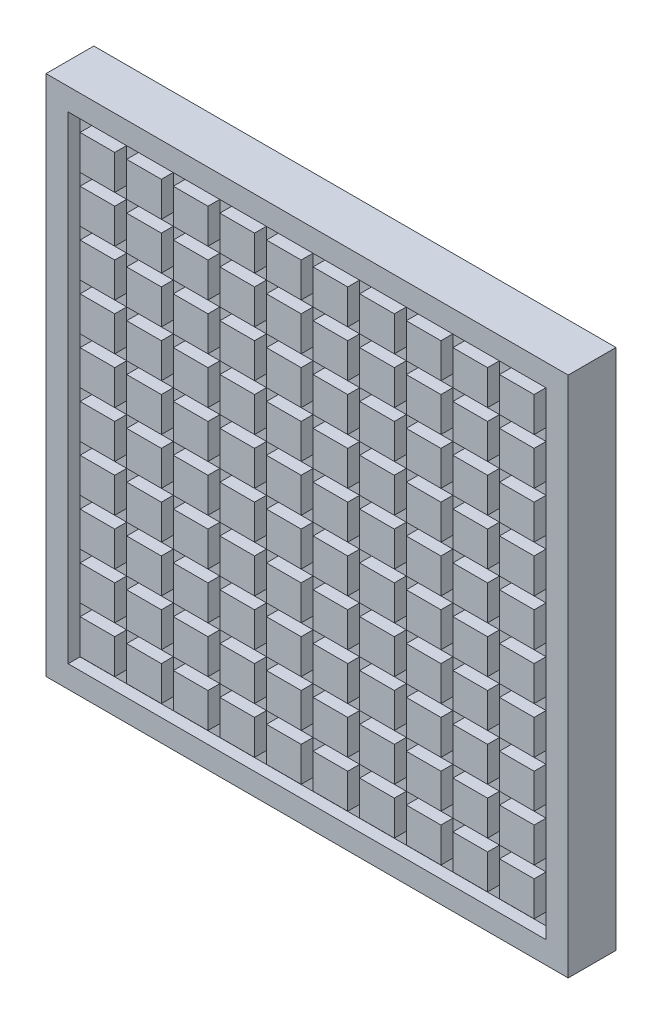
SolidWorks part; units mm, degrees
ref_plane "前视基准面" through (0, 0, 0) normal (0, 0, 1) x (1, 0, 0)
ref_plane "上视基准面" through (0, 0, 0) normal (0, 1, 0) x (1, 0, 0)
ref_plane "右视基准面" through (0, 0, 0) normal (1, 0, 0) x (0, 0, -1)
other "Configuration Table"
sketch "草图1" plane through (0, 0, 0) normal (0, 0, 1) x (1, 0, 0)
  line L1 (0, 0) -> (437, 0)
  line L2 (0, 0) -> (0, 437)
  line L3 (0, 437) -> (437, 437)
  line L4 (437, 0) -> (437, 437)
extrude "凸台-拉伸1" add sketch "草图1" along normal blind 40
ref_point "点2"
sketch "草图2" plane through (0, 0, 0) normal (-1, 0, 0) x (0, 0, 1)
  line L0 (20, 218.5) -> (8.3215, 218.5)
ref_axis "基准轴1" through (0, 218.5, 20) along (0, 0, -1)
ref_axis "基准轴2" through (0, 218.5, 20) along (-1, 0, 0)
sketch "草图3" plane through (0, 0, 40) normal (0, 0, 1) x (1, 0, 0)
  line L25 (18.5, 418.5) -> (418.5, 418.5)
  line L26 (18.5, 418.5) -> (18.5, 18.5)
  line L27 (18.5, 18.5) -> (418.5, 18.5)
  line L28 (418.5, 418.5) -> (418.5, 18.5)
extrude "切除-拉伸1" cut sketch "草图3" against normal blind 10
sketch "草图4" plane through (0, 0, 30) normal (0, 0, 1) x (1, 0, 0)
  line L0 (67.5, 408.6283) -> (67.5, 379.6283)
  line L5 (28.5, 408.6283) -> (57.5, 408.6283)
  line L6 (28.5, 408.6283) -> (28.5, 379.6283)
  line L7 (28.5, 379.6283) -> (57.5, 379.6283)
  line L8 (57.5, 408.6283) -> (57.5, 379.6283)
  line L9 (67.5, 408.6283) -> (96.5, 408.6283)
  line L10 (96.5, 408.6283) -> (96.5, 379.6283)
  line L11 (67.5, 379.6283) -> (96.5, 379.6283)
  line L12 (106.5, 408.6283) -> (106.5, 379.6283)
  line L13 (106.5, 408.6283) -> (135.5, 408.6283)
  line L14 (135.5, 408.6283) -> (135.5, 379.6283)
  line L15 (106.5, 379.6283) -> (135.5, 379.6283)
  line L16 (145.5, 408.6283) -> (145.5, 379.6283)
  line L17 (145.5, 408.6283) -> (174.5, 408.6283)
  line L18 (174.5, 408.6283) -> (174.5, 379.6283)
  line L19 (145.5, 379.6283) -> (174.5, 379.6283)
  line L20 (184.5, 408.6283) -> (184.5, 379.6283)
  line L21 (184.5, 408.6283) -> (213.5, 408.6283)
  line L22 (213.5, 408.6283) -> (213.5, 379.6283)
  line L23 (184.5, 379.6283) -> (213.5, 379.6283)
  line L24 (223.5, 408.6283) -> (223.5, 379.6283)
  line L25 (223.5, 408.6283) -> (252.5, 408.6283)
  line L26 (252.5, 408.6283) -> (252.5, 379.6283)
  line L27 (223.5, 379.6283) -> (252.5, 379.6283)
  line L28 (262.5, 408.6283) -> (262.5, 379.6283)
  line L29 (262.5, 408.6283) -> (291.5, 408.6283)
  line L30 (291.5, 408.6283) -> (291.5, 379.6283)
  line L31 (262.5, 379.6283) -> (291.5, 379.6283)
  line L32 (301.5, 408.6283) -> (301.5, 379.6283)
  line L33 (301.5, 408.6283) -> (330.5, 408.6283)
  line L34 (330.5, 408.6283) -> (330.5, 379.6283)
  line L35 (301.5, 379.6283) -> (330.5, 379.6283)
  line L36 (340.5, 408.6283) -> (340.5, 379.6283)
  line L37 (340.5, 408.6283) -> (369.5, 408.6283)
  line L38 (369.5, 408.6283) -> (369.5, 379.6283)
  line L39 (340.5, 379.6283) -> (369.5, 379.6283)
  line L40 (379.5, 408.6283) -> (379.5, 379.6283)
  line L41 (379.5, 408.6283) -> (408.5, 408.6283)
  line L42 (408.5, 408.6283) -> (408.5, 379.6283)
  line L43 (379.5, 379.6283) -> (408.5, 379.6283)
  line L44 (67.5, 369.6283) -> (67.5, 340.6283)
  line L45 (67.5, 369.6283) -> (96.5, 369.6283)
  line L46 (96.5, 369.6283) -> (96.5, 340.6283)
  line L47 (67.5, 340.6283) -> (96.5, 340.6283)
  line L48 (106.5, 369.6283) -> (106.5, 340.6283)
  line L49 (106.5, 369.6283) -> (135.5, 369.6283)
  line L50 (135.5, 369.6283) -> (135.5, 340.6283)
  line L51 (106.5, 340.6283) -> (135.5, 340.6283)
  line L52 (145.5, 369.6283) -> (145.5, 340.6283)
  line L53 (145.5, 369.6283) -> (174.5, 369.6283)
  line L54 (174.5, 369.6283) -> (174.5, 340.6283)
  line L55 (145.5, 340.6283) -> (174.5, 340.6283)
  line L56 (184.5, 369.6283) -> (184.5, 340.6283)
  line L57 (184.5, 369.6283) -> (213.5, 369.6283)
  line L58 (213.5, 369.6283) -> (213.5, 340.6283)
  line L59 (184.5, 340.6283) -> (213.5, 340.6283)
  line L60 (223.5, 369.6283) -> (223.5, 340.6283)
  line L61 (223.5, 369.6283) -> (252.5, 369.6283)
  line L62 (252.5, 369.6283) -> (252.5, 340.6283)
  line L63 (223.5, 340.6283) -> (252.5, 340.6283)
  line L64 (262.5, 369.6283) -> (262.5, 340.6283)
  line L65 (262.5, 369.6283) -> (291.5, 369.6283)
  line L66 (291.5, 369.6283) -> (291.5, 340.6283)
  line L67 (262.5, 340.6283) -> (291.5, 340.6283)
  line L68 (301.5, 369.6283) -> (301.5, 340.6283)
  line L69 (301.5, 369.6283) -> (330.5, 369.6283)
  line L70 (330.5, 369.6283) -> (330.5, 340.6283)
  line L71 (301.5, 340.6283) -> (330.5, 340.6283)
  line L72 (340.5, 369.6283) -> (340.5, 340.6283)
  line L73 (340.5, 369.6283) -> (369.5, 369.6283)
  line L74 (369.5, 369.6283) -> (369.5, 340.6283)
  line L75 (340.5, 340.6283) -> (369.5, 340.6283)
  line L76 (379.5, 369.6283) -> (379.5, 340.6283)
  line L77 (379.5, 369.6283) -> (408.5, 369.6283)
  line L78 (408.5, 369.6283) -> (408.5, 340.6283)
  line L79 (379.5, 340.6283) -> (408.5, 340.6283)
  line L80 (67.5, 330.6283) -> (67.5, 301.6283)
  line L81 (67.5, 330.6283) -> (96.5, 330.6283)
  line L82 (96.5, 330.6283) -> (96.5, 301.6283)
  line L83 (67.5, 301.6283) -> (96.5, 301.6283)
  line L84 (106.5, 330.6283) -> (106.5, 301.6283)
  line L85 (106.5, 330.6283) -> (135.5, 330.6283)
  line L86 (135.5, 330.6283) -> (135.5, 301.6283)
  line L87 (106.5, 301.6283) -> (135.5, 301.6283)
  line L88 (145.5, 330.6283) -> (145.5, 301.6283)
  line L89 (145.5, 330.6283) -> (174.5, 330.6283)
  line L90 (174.5, 330.6283) -> (174.5, 301.6283)
  line L91 (145.5, 301.6283) -> (174.5, 301.6283)
  line L92 (184.5, 330.6283) -> (184.5, 301.6283)
  line L93 (184.5, 330.6283) -> (213.5, 330.6283)
  line L94 (213.5, 330.6283) -> (213.5, 301.6283)
  line L95 (184.5, 301.6283) -> (213.5, 301.6283)
  line L96 (223.5, 330.6283) -> (223.5, 301.6283)
  line L97 (223.5, 330.6283) -> (252.5, 330.6283)
  line L98 (252.5, 330.6283) -> (252.5, 301.6283)
  line L99 (223.5, 301.6283) -> (252.5, 301.6283)
  line L100 (262.5, 330.6283) -> (262.5, 301.6283)
  line L101 (262.5, 330.6283) -> (291.5, 330.6283)
  line L102 (291.5, 330.6283) -> (291.5, 301.6283)
  line L103 (262.5, 301.6283) -> (291.5, 301.6283)
  line L104 (301.5, 330.6283) -> (301.5, 301.6283)
  line L105 (301.5, 330.6283) -> (330.5, 330.6283)
  line L106 (330.5, 330.6283) -> (330.5, 301.6283)
  line L107 (301.5, 301.6283) -> (330.5, 301.6283)
  line L108 (340.5, 330.6283) -> (340.5, 301.6283)
  line L109 (340.5, 330.6283) -> (369.5, 330.6283)
  line L110 (369.5, 330.6283) -> (369.5, 301.6283)
  line L111 (340.5, 301.6283) -> (369.5, 301.6283)
  line L112 (379.5, 330.6283) -> (379.5, 301.6283)
  line L113 (379.5, 330.6283) -> (408.5, 330.6283)
  line L114 (408.5, 330.6283) -> (408.5, 301.6283)
  line L115 (379.5, 301.6283) -> (408.5, 301.6283)
  line L116 (67.5, 291.6283) -> (67.5, 262.6283)
  line L117 (67.5, 291.6283) -> (96.5, 291.6283)
  line L118 (96.5, 291.6283) -> (96.5, 262.6283)
  line L119 (67.5, 262.6283) -> (96.5, 262.6283)
  line L120 (106.5, 291.6283) -> (106.5, 262.6283)
  line L121 (106.5, 291.6283) -> (135.5, 291.6283)
  line L122 (135.5, 291.6283) -> (135.5, 262.6283)
  line L123 (106.5, 262.6283) -> (135.5, 262.6283)
  line L124 (145.5, 291.6283) -> (145.5, 262.6283)
  line L125 (145.5, 291.6283) -> (174.5, 291.6283)
  line L126 (174.5, 291.6283) -> (174.5, 262.6283)
  line L127 (145.5, 262.6283) -> (174.5, 262.6283)
  line L128 (184.5, 291.6283) -> (184.5, 262.6283)
  line L129 (184.5, 291.6283) -> (213.5, 291.6283)
  line L130 (213.5, 291.6283) -> (213.5, 262.6283)
  line L131 (184.5, 262.6283) -> (213.5, 262.6283)
  line L132 (223.5, 291.6283) -> (223.5, 262.6283)
  line L133 (223.5, 291.6283) -> (252.5, 291.6283)
  line L134 (252.5, 291.6283) -> (252.5, 262.6283)
  line L135 (223.5, 262.6283) -> (252.5, 262.6283)
  line L136 (262.5, 291.6283) -> (262.5, 262.6283)
  line L137 (262.5, 291.6283) -> (291.5, 291.6283)
  line L138 (291.5, 291.6283) -> (291.5, 262.6283)
  line L139 (262.5, 262.6283) -> (291.5, 262.6283)
  line L140 (301.5, 291.6283) -> (301.5, 262.6283)
  line L141 (301.5, 291.6283) -> (330.5, 291.6283)
  line L142 (330.5, 291.6283) -> (330.5, 262.6283)
  line L143 (301.5, 262.6283) -> (330.5, 262.6283)
  line L144 (340.5, 291.6283) -> (340.5, 262.6283)
  line L145 (340.5, 291.6283) -> (369.5, 291.6283)
  line L146 (369.5, 291.6283) -> (369.5, 262.6283)
  line L147 (340.5, 262.6283) -> (369.5, 262.6283)
  line L148 (379.5, 291.6283) -> (379.5, 262.6283)
  line L149 (379.5, 291.6283) -> (408.5, 291.6283)
  line L150 (408.5, 291.6283) -> (408.5, 262.6283)
  line L151 (379.5, 262.6283) -> (408.5, 262.6283)
  line L152 (67.5, 252.6283) -> (67.5, 223.6283)
  line L153 (67.5, 252.6283) -> (96.5, 252.6283)
  line L154 (96.5, 252.6283) -> (96.5, 223.6283)
  line L155 (67.5, 223.6283) -> (96.5, 223.6283)
  line L156 (106.5, 252.6283) -> (106.5, 223.6283)
  line L157 (106.5, 252.6283) -> (135.5, 252.6283)
  line L158 (135.5, 252.6283) -> (135.5, 223.6283)
  line L159 (106.5, 223.6283) -> (135.5, 223.6283)
  line L160 (145.5, 252.6283) -> (145.5, 223.6283)
  line L161 (145.5, 252.6283) -> (174.5, 252.6283)
  line L162 (174.5, 252.6283) -> (174.5, 223.6283)
  line L163 (145.5, 223.6283) -> (174.5, 223.6283)
  line L164 (184.5, 252.6283) -> (184.5, 223.6283)
  line L165 (184.5, 252.6283) -> (213.5, 252.6283)
  line L166 (213.5, 252.6283) -> (213.5, 223.6283)
  line L167 (184.5, 223.6283) -> (213.5, 223.6283)
  line L168 (223.5, 252.6283) -> (223.5, 223.6283)
  line L169 (223.5, 252.6283) -> (252.5, 252.6283)
  line L170 (252.5, 252.6283) -> (252.5, 223.6283)
  line L171 (223.5, 223.6283) -> (252.5, 223.6283)
  line L172 (262.5, 252.6283) -> (262.5, 223.6283)
  line L173 (262.5, 252.6283) -> (291.5, 252.6283)
  line L174 (291.5, 252.6283) -> (291.5, 223.6283)
  line L175 (262.5, 223.6283) -> (291.5, 223.6283)
  line L176 (301.5, 252.6283) -> (301.5, 223.6283)
  line L177 (301.5, 252.6283) -> (330.5, 252.6283)
  line L178 (330.5, 252.6283) -> (330.5, 223.6283)
  line L179 (301.5, 223.6283) -> (330.5, 223.6283)
  line L180 (340.5, 252.6283) -> (340.5, 223.6283)
  line L181 (340.5, 252.6283) -> (369.5, 252.6283)
  line L182 (369.5, 252.6283) -> (369.5, 223.6283)
  line L183 (340.5, 223.6283) -> (369.5, 223.6283)
  line L184 (379.5, 252.6283) -> (379.5, 223.6283)
  line L185 (379.5, 252.6283) -> (408.5, 252.6283)
  line L186 (408.5, 252.6283) -> (408.5, 223.6283)
  line L187 (379.5, 223.6283) -> (408.5, 223.6283)
  line L188 (67.5, 213.6283) -> (67.5, 184.6283)
  line L189 (67.5, 213.6283) -> (96.5, 213.6283)
  line L190 (96.5, 213.6283) -> (96.5, 184.6283)
  line L191 (67.5, 184.6283) -> (96.5, 184.6283)
  line L192 (106.5, 213.6283) -> (106.5, 184.6283)
  line L193 (106.5, 213.6283) -> (135.5, 213.6283)
  line L194 (135.5, 213.6283) -> (135.5, 184.6283)
  line L195 (106.5, 184.6283) -> (135.5, 184.6283)
  line L196 (145.5, 213.6283) -> (145.5, 184.6283)
  line L197 (145.5, 213.6283) -> (174.5, 213.6283)
  line L198 (174.5, 213.6283) -> (174.5, 184.6283)
  line L199 (145.5, 184.6283) -> (174.5, 184.6283)
  line L200 (184.5, 213.6283) -> (184.5, 184.6283)
  line L201 (184.5, 213.6283) -> (213.5, 213.6283)
  line L202 (213.5, 213.6283) -> (213.5, 184.6283)
  line L203 (184.5, 184.6283) -> (213.5, 184.6283)
  line L204 (223.5, 213.6283) -> (223.5, 184.6283)
  line L205 (223.5, 213.6283) -> (252.5, 213.6283)
  line L206 (252.5, 213.6283) -> (252.5, 184.6283)
  line L207 (223.5, 184.6283) -> (252.5, 184.6283)
  line L208 (262.5, 213.6283) -> (262.5, 184.6283)
  line L209 (262.5, 213.6283) -> (291.5, 213.6283)
  line L210 (291.5, 213.6283) -> (291.5, 184.6283)
  line L211 (262.5, 184.6283) -> (291.5, 184.6283)
  line L212 (301.5, 213.6283) -> (301.5, 184.6283)
  line L213 (301.5, 213.6283) -> (330.5, 213.6283)
  line L214 (330.5, 213.6283) -> (330.5, 184.6283)
  line L215 (301.5, 184.6283) -> (330.5, 184.6283)
  line L216 (340.5, 213.6283) -> (340.5, 184.6283)
  line L217 (340.5, 213.6283) -> (369.5, 213.6283)
  line L218 (369.5, 213.6283) -> (369.5, 184.6283)
  line L219 (340.5, 184.6283) -> (369.5, 184.6283)
  line L220 (379.5, 213.6283) -> (379.5, 184.6283)
  line L221 (379.5, 213.6283) -> (408.5, 213.6283)
  line L222 (408.5, 213.6283) -> (408.5, 184.6283)
  line L223 (379.5, 184.6283) -> (408.5, 184.6283)
  line L224 (67.5, 174.6283) -> (67.5, 145.6283)
  line L225 (67.5, 174.6283) -> (96.5, 174.6283)
  line L226 (96.5, 174.6283) -> (96.5, 145.6283)
  line L227 (67.5, 145.6283) -> (96.5, 145.6283)
  line L228 (106.5, 174.6283) -> (106.5, 145.6283)
  line L229 (106.5, 174.6283) -> (135.5, 174.6283)
  line L230 (135.5, 174.6283) -> (135.5, 145.6283)
  line L231 (106.5, 145.6283) -> (135.5, 145.6283)
  line L232 (145.5, 174.6283) -> (145.5, 145.6283)
  line L233 (145.5, 174.6283) -> (174.5, 174.6283)
  line L234 (174.5, 174.6283) -> (174.5, 145.6283)
  line L235 (145.5, 145.6283) -> (174.5, 145.6283)
  line L236 (184.5, 174.6283) -> (184.5, 145.6283)
  line L237 (184.5, 174.6283) -> (213.5, 174.6283)
  line L238 (213.5, 174.6283) -> (213.5, 145.6283)
  line L239 (184.5, 145.6283) -> (213.5, 145.6283)
  line L240 (223.5, 174.6283) -> (223.5, 145.6283)
  line L241 (223.5, 174.6283) -> (252.5, 174.6283)
  line L242 (252.5, 174.6283) -> (252.5, 145.6283)
  line L243 (223.5, 145.6283) -> (252.5, 145.6283)
  line L244 (262.5, 174.6283) -> (262.5, 145.6283)
  line L245 (262.5, 174.6283) -> (291.5, 174.6283)
  line L246 (291.5, 174.6283) -> (291.5, 145.6283)
  line L247 (262.5, 145.6283) -> (291.5, 145.6283)
  line L248 (301.5, 174.6283) -> (301.5, 145.6283)
  line L249 (301.5, 174.6283) -> (330.5, 174.6283)
  line L250 (330.5, 174.6283) -> (330.5, 145.6283)
  line L251 (301.5, 145.6283) -> (330.5, 145.6283)
  line L252 (340.5, 174.6283) -> (340.5, 145.6283)
  line L253 (340.5, 174.6283) -> (369.5, 174.6283)
  line L254 (369.5, 174.6283) -> (369.5, 145.6283)
  line L255 (340.5, 145.6283) -> (369.5, 145.6283)
  line L256 (379.5, 174.6283) -> (379.5, 145.6283)
  line L257 (379.5, 174.6283) -> (408.5, 174.6283)
  line L258 (408.5, 174.6283) -> (408.5, 145.6283)
  line L259 (379.5, 145.6283) -> (408.5, 145.6283)
  line L260 (67.5, 135.6283) -> (67.5, 106.6283)
  line L261 (67.5, 135.6283) -> (96.5, 135.6283)
  line L262 (96.5, 135.6283) -> (96.5, 106.6283)
  line L263 (67.5, 106.6283) -> (96.5, 106.6283)
  line L264 (106.5, 135.6283) -> (106.5, 106.6283)
  line L265 (106.5, 135.6283) -> (135.5, 135.6283)
  line L266 (135.5, 135.6283) -> (135.5, 106.6283)
  line L267 (106.5, 106.6283) -> (135.5, 106.6283)
  line L268 (145.5, 135.6283) -> (145.5, 106.6283)
  line L269 (145.5, 135.6283) -> (174.5, 135.6283)
  line L270 (174.5, 135.6283) -> (174.5, 106.6283)
  line L271 (145.5, 106.6283) -> (174.5, 106.6283)
  line L272 (184.5, 135.6283) -> (184.5, 106.6283)
  line L273 (184.5, 135.6283) -> (213.5, 135.6283)
  line L274 (213.5, 135.6283) -> (213.5, 106.6283)
  line L275 (184.5, 106.6283) -> (213.5, 106.6283)
  line L276 (223.5, 135.6283) -> (223.5, 106.6283)
  line L277 (223.5, 135.6283) -> (252.5, 135.6283)
  line L278 (252.5, 135.6283) -> (252.5, 106.6283)
  line L279 (223.5, 106.6283) -> (252.5, 106.6283)
  line L280 (262.5, 135.6283) -> (262.5, 106.6283)
  line L281 (262.5, 135.6283) -> (291.5, 135.6283)
  line L282 (291.5, 135.6283) -> (291.5, 106.6283)
  line L283 (262.5, 106.6283) -> (291.5, 106.6283)
  line L284 (301.5, 135.6283) -> (301.5, 106.6283)
  line L285 (301.5, 135.6283) -> (330.5, 135.6283)
  line L286 (330.5, 135.6283) -> (330.5, 106.6283)
  line L287 (301.5, 106.6283) -> (330.5, 106.6283)
  line L288 (340.5, 135.6283) -> (340.5, 106.6283)
  line L289 (340.5, 135.6283) -> (369.5, 135.6283)
  line L290 (369.5, 135.6283) -> (369.5, 106.6283)
  line L291 (340.5, 106.6283) -> (369.5, 106.6283)
  line L292 (379.5, 135.6283) -> (379.5, 106.6283)
  line L293 (379.5, 135.6283) -> (408.5, 135.6283)
  line L294 (408.5, 135.6283) -> (408.5, 106.6283)
  line L295 (379.5, 106.6283) -> (408.5, 106.6283)
  line L296 (67.5, 96.6283) -> (67.5, 67.6283)
  line L297 (67.5, 96.6283) -> (96.5, 96.6283)
  line L298 (96.5, 96.6283) -> (96.5, 67.6283)
  line L299 (67.5, 67.6283) -> (96.5, 67.6283)
  line L300 (106.5, 96.6283) -> (106.5, 67.6283)
  line L301 (106.5, 96.6283) -> (135.5, 96.6283)
  line L302 (135.5, 96.6283) -> (135.5, 67.6283)
  line L303 (106.5, 67.6283) -> (135.5, 67.6283)
  line L304 (145.5, 96.6283) -> (145.5, 67.6283)
  line L305 (145.5, 96.6283) -> (174.5, 96.6283)
  line L306 (174.5, 96.6283) -> (174.5, 67.6283)
  line L307 (145.5, 67.6283) -> (174.5, 67.6283)
  line L308 (184.5, 96.6283) -> (184.5, 67.6283)
  line L309 (184.5, 96.6283) -> (213.5, 96.6283)
  line L310 (213.5, 96.6283) -> (213.5, 67.6283)
  line L311 (184.5, 67.6283) -> (213.5, 67.6283)
  line L312 (223.5, 96.6283) -> (223.5, 67.6283)
  line L313 (223.5, 96.6283) -> (252.5, 96.6283)
  line L314 (252.5, 96.6283) -> (252.5, 67.6283)
  line L315 (223.5, 67.6283) -> (252.5, 67.6283)
  line L316 (262.5, 96.6283) -> (262.5, 67.6283)
  line L317 (262.5, 96.6283) -> (291.5, 96.6283)
  line L318 (291.5, 96.6283) -> (291.5, 67.6283)
  line L319 (262.5, 67.6283) -> (291.5, 67.6283)
  line L320 (301.5, 96.6283) -> (301.5, 67.6283)
  line L321 (301.5, 96.6283) -> (330.5, 96.6283)
  line L322 (330.5, 96.6283) -> (330.5, 67.6283)
  line L323 (301.5, 67.6283) -> (330.5, 67.6283)
  line L324 (340.5, 96.6283) -> (340.5, 67.6283)
  line L325 (340.5, 96.6283) -> (369.5, 96.6283)
  line L326 (369.5, 96.6283) -> (369.5, 67.6283)
  line L327 (340.5, 67.6283) -> (369.5, 67.6283)
  line L328 (379.5, 96.6283) -> (379.5, 67.6283)
  line L329 (379.5, 96.6283) -> (408.5, 96.6283)
  line L330 (408.5, 96.6283) -> (408.5, 67.6283)
  line L331 (379.5, 67.6283) -> (408.5, 67.6283)
  line L332 (67.5, 57.6283) -> (67.5, 28.6283)
  line L333 (67.5, 57.6283) -> (96.5, 57.6283)
  line L334 (96.5, 57.6283) -> (96.5, 28.6283)
  line L335 (67.5, 28.6283) -> (96.5, 28.6283)
  line L336 (106.5, 57.6283) -> (106.5, 28.6283)
  line L337 (106.5, 57.6283) -> (135.5, 57.6283)
  line L338 (135.5, 57.6283) -> (135.5, 28.6283)
  line L339 (106.5, 28.6283) -> (135.5, 28.6283)
  line L340 (145.5, 57.6283) -> (145.5, 28.6283)
  line L341 (145.5, 57.6283) -> (174.5, 57.6283)
  line L342 (174.5, 57.6283) -> (174.5, 28.6283)
  line L343 (145.5, 28.6283) -> (174.5, 28.6283)
  line L344 (184.5, 57.6283) -> (184.5, 28.6283)
  line L345 (184.5, 57.6283) -> (213.5, 57.6283)
  line L346 (213.5, 57.6283) -> (213.5, 28.6283)
  line L347 (184.5, 28.6283) -> (213.5, 28.6283)
  line L348 (223.5, 57.6283) -> (223.5, 28.6283)
  line L349 (223.5, 57.6283) -> (252.5, 57.6283)
  line L350 (252.5, 57.6283) -> (252.5, 28.6283)
  line L351 (223.5, 28.6283) -> (252.5, 28.6283)
  line L352 (262.5, 57.6283) -> (262.5, 28.6283)
  line L353 (262.5, 57.6283) -> (291.5, 57.6283)
  line L354 (291.5, 57.6283) -> (291.5, 28.6283)
  line L355 (262.5, 28.6283) -> (291.5, 28.6283)
  line L356 (301.5, 57.6283) -> (301.5, 28.6283)
  line L357 (301.5, 57.6283) -> (330.5, 57.6283)
  line L358 (330.5, 57.6283) -> (330.5, 28.6283)
  line L359 (301.5, 28.6283) -> (330.5, 28.6283)
  line L360 (340.5, 57.6283) -> (340.5, 28.6283)
  line L361 (340.5, 57.6283) -> (369.5, 57.6283)
  line L362 (369.5, 57.6283) -> (369.5, 28.6283)
  line L363 (340.5, 28.6283) -> (369.5, 28.6283)
  line L364 (379.5, 57.6283) -> (379.5, 28.6283)
  line L365 (379.5, 57.6283) -> (408.5, 57.6283)
  line L366 (408.5, 57.6283) -> (408.5, 28.6283)
  line L367 (379.5, 28.6283) -> (408.5, 28.6283)
  line L368 (28.5, 369.6283) -> (28.5, 340.6283)
  line L369 (28.5, 369.6283) -> (57.5, 369.6283)
  line L370 (57.5, 369.6283) -> (57.5, 340.6283)
  line L371 (28.5, 340.6283) -> (57.5, 340.6283)
  line L372 (28.5, 330.6283) -> (28.5, 301.6283)
  line L373 (28.5, 330.6283) -> (57.5, 330.6283)
  line L374 (57.5, 330.6283) -> (57.5, 301.6283)
  line L375 (28.5, 301.6283) -> (57.5, 301.6283)
  line L376 (28.5, 291.6283) -> (28.5, 262.6283)
  line L377 (28.5, 291.6283) -> (57.5, 291.6283)
  line L378 (57.5, 291.6283) -> (57.5, 262.6283)
  line L379 (28.5, 262.6283) -> (57.5, 262.6283)
  line L380 (28.5, 252.6283) -> (28.5, 223.6283)
  line L381 (28.5, 252.6283) -> (57.5, 252.6283)
  line L382 (57.5, 252.6283) -> (57.5, 223.6283)
  line L383 (28.5, 223.6283) -> (57.5, 223.6283)
  line L384 (28.5, 213.6283) -> (28.5, 184.6283)
  line L385 (28.5, 213.6283) -> (57.5, 213.6283)
  line L386 (57.5, 213.6283) -> (57.5, 184.6283)
  line L387 (28.5, 184.6283) -> (57.5, 184.6283)
  line L388 (28.5, 174.6283) -> (28.5, 145.6283)
  line L389 (28.5, 174.6283) -> (57.5, 174.6283)
  line L390 (57.5, 174.6283) -> (57.5, 145.6283)
  line L391 (28.5, 145.6283) -> (57.5, 145.6283)
  line L392 (28.5, 135.6283) -> (28.5, 106.6283)
  line L393 (28.5, 135.6283) -> (57.5, 135.6283)
  line L394 (57.5, 135.6283) -> (57.5, 106.6283)
  line L395 (28.5, 106.6283) -> (57.5, 106.6283)
  line L396 (28.5, 96.6283) -> (28.5, 67.6283)
  line L397 (28.5, 96.6283) -> (57.5, 96.6283)
  line L398 (57.5, 96.6283) -> (57.5, 67.6283)
  line L399 (28.5, 67.6283) -> (57.5, 67.6283)
  line L400 (28.5, 57.6283) -> (28.5, 28.6283)
  line L401 (28.5, 57.6283) -> (57.5, 57.6283)
  line L402 (57.5, 57.6283) -> (57.5, 28.6283)
  line L403 (28.5, 28.6283) -> (57.5, 28.6283)
  dimension "D1" = 10
  dimension "D2" = 10
extrude "凸台-拉伸2" add sketch "草图4" along normal blind 10
